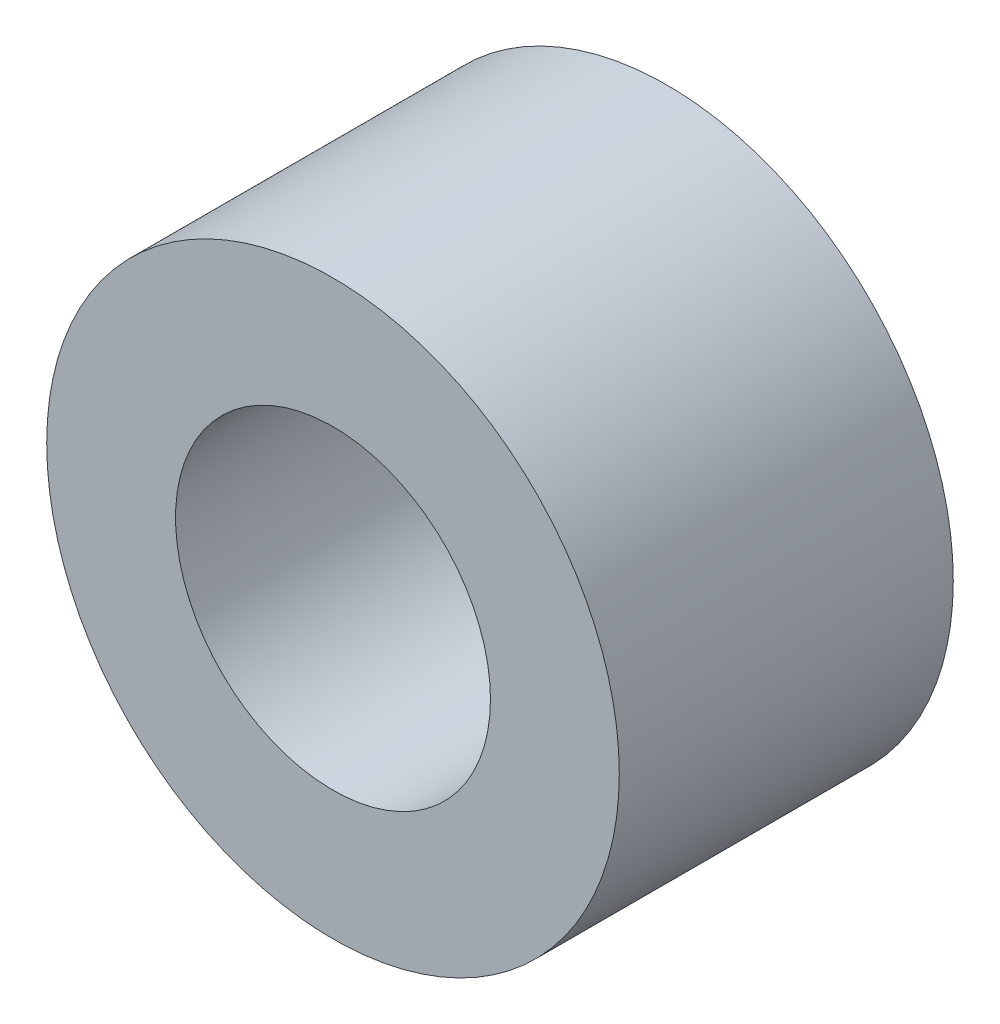
SolidWorks part; units mm, degrees
material "Nylon 101"
ref_plane "Front Plane" through (0, 0, 0) normal (0, 0, 1) x (1, 0, 0)
ref_plane "Top Plane" through (0, 0, 0) normal (0, 1, 0) x (1, 0, 0)
ref_plane "Right Plane" through (0, 0, 0) normal (1, 0, 0) x (0, 0, -1)
sketch "Sketch1" plane through (0, 0, 0) normal (0, 0, 1) x (1, 0, 0)
  circle A0 centre (0, 0) radius 9.525
  circle A1 centre (0, 0) radius 5.2387
  dimension "D1" = 19.05
  dimension "D2" = 10.4775
extrude "Boss-Extrude1" add sketch "Sketch1" along normal mid plane 11.1125
equation "\"D1@Boss-Extrude1\"=0.0625in+0.45mm/2"
